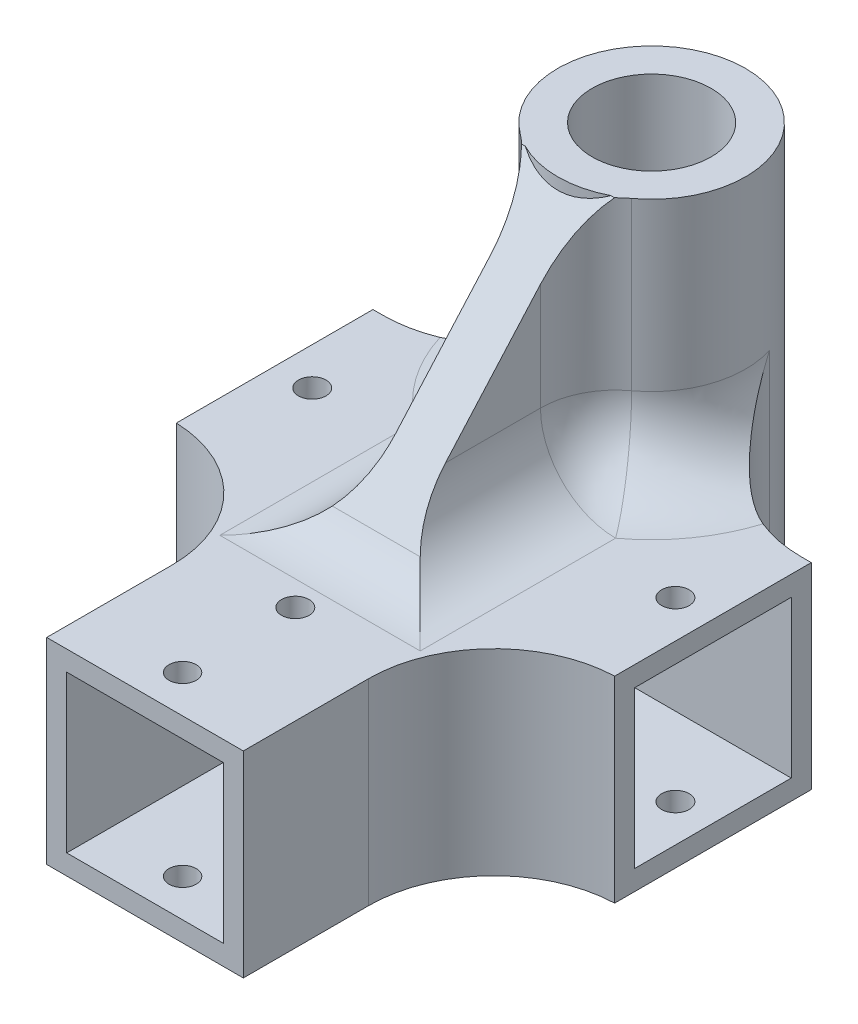
SolidWorks part; units mm, degrees
ref_plane "Front" through (0, 0, 0) normal (0, 0, 1) x (1, 0, 0)
ref_plane "Top" through (0, 0, 0) normal (0, 1, 0) x (1, 0, 0)
ref_plane "Right" through (0, 0, 0) normal (1, 0, 0) x (0, 0, -1)
sketch "Эскиз1" plane through (0, 0, 0) normal (1, 0, 0) x (0, 0, -1)
  line L1 (-12.5, -12.5) -> (12.5, -12.5)
  line L2 (-12.5, -12.5) -> (-12.5, 12.5)
  line L3 (-12.5, 12.5) -> (12.5, 12.5)
  line L4 (12.5, -12.5) -> (12.5, 12.5)
  line L5 (-12.5, -12.5) -> (12.5, 12.5) construction
  line L6 (-12.5, 12.5) -> (12.5, -12.5) construction
  point P0 (0, 0)
  dimension "D1" = 25
  dimension "D2" = 25
extrude "Вытянуть-Тонкостенный1" add sketch "Эскиз1" along normal blind 70 thin thin type one direction wall 3.2
sketch "Эскиз2" plane through (0, 0, 15.7) normal (0, 0, 1) x (1, 0, 0)
  line L0 (35, 15.7) -> (35, -15.7) construction
  line L1 (70, 15.7) -> (0, 15.7) construction
  line L2 (70, -15.7) -> (0, -15.7) construction
  line L4 (22.5, 12.5) -> (47.5, 12.5)
  line L5 (22.5, 12.5) -> (22.5, -12.5)
  line L6 (22.5, -12.5) -> (47.5, -12.5)
  line L7 (47.5, 12.5) -> (47.5, -12.5)
  line L8 (22.5, 12.5) -> (47.5, -12.5) construction
  line L9 (22.5, -12.5) -> (47.5, 12.5) construction
  point P6 (35, 0)
  dimension "D1" = 25
  dimension "D2" = 25
extrude "Вытянуть-Тонкостенный2" add sketch "Эскиз2" along normal blind 40 thin thin type one direction wall 3.2
sketch "Эскиз3" plane through (0, 0, 15.7) normal (0, 0, 1) x (1, 0, 0)
  line L1 (22.5, 12.5) -> (47.5, 12.5)
  line L2 (22.5, 12.5) -> (22.5, -12.5)
  line L3 (22.5, -12.5) -> (47.5, -12.5)
  line L4 (47.5, 12.5) -> (47.5, -12.5)
extrude "Вырез-Вытянуть1" cut sketch "Эскиз3" against normal up to next
fillet "Скругление1" radius 20 2 edges at (50.7, 0, 15.7) (19.3, 0, 15.7)
sketch "Эскиз4" plane through (0, -15.7, 0) normal (0, -1, 0) x (1, 0, 0)
  line L0 (35, 55.7) -> (35, -32.8587) construction
  line L1 (19.3, 55.7) -> (50.7, 55.7) construction
  line L2 (70, -15.7) -> (0, -15.7) construction
  circle A0 centre (35, -25.2) radius 9.5
  circle A1 centre (35, -25.2) radius 15
  dimension "D1" = 19
  dimension "D2" = 9.5
extrude "Бобышка-Вытянуть1" add sketch "Эскиз4" against normal blind 70
sketch "Эскиз5" plane through (0, 0, 0) normal (-1, 0, 0) x (0, 0, 1)
  line L1 (-12.5, 12.5) -> (-10.2, 12.5)
  line L2 (-12.5, 12.5) -> (-12.5, -12.5)
  line L3 (-12.5, -12.5) -> (-10.2, -12.5)
  line L4 (-10.2, 12.5) -> (-10.2, -12.5)
extrude "Вырез-Вытянуть2" cut sketch "Эскиз5" against normal up to next
sketch "Эскиз6" plane through (0, 0, 0) normal (-1, 0, 0) x (0, 0, 1)
  line L0 (-11.8488, 54.3) -> (-11.8488, 15.7)
  line L1 (-11.8488, 54.3) -> (22.349, 15.7)
  line L2 (-15.7, 15.7) -> (15.7, 15.7) construction
  line L3 (-11.8488, 15.7) -> (22.349, 15.7)
  line L5 (-10.2, 54.3) -> (-40.2, 54.3) construction
  line L8 (35.6877, 15.7) -> (15.7, 15.7) construction
extrude "Бобышка-Вытянуть3" add sketch "Эскиз6" against normal blind 8 from offset 31 offset against normal yes
fillet "Скругление2" radius 12 3 edges at (31, 34.376, -10.7432) (39, 34.376, -10.7432) (35, 15.7, 22.349)
fillet "Скругление3" radius 12 6 edges at (39, 15.7, 12.1491) (40.2917, 15.7, -8.8675) (31, 15.7, 12.1491) (29.7083, 15.7, -8.8675) (45.3296, 15.7, -14.3234) (24.6704, 15.7, -14.3234)
sketch "Эскиз7" plane through (0, 15.7, 0) normal (0, 1, 0) x (1, 0, 0)
  line L0 (0, 0) -> (70, 0) construction
  line L1 (0, 15.7) -> (0, -15.7) construction
  line L2 (70, 15.7) -> (70, -15.7) construction
  line L3 (35, -55.7) -> (35, 0) construction
  line L4 (50.7, -55.7) -> (19.3, -55.7) construction
  circle A0 centre (6, 0) radius 2.2
  circle A1 centre (64, 0) radius 2.2
  circle A2 centre (35, -49.7) radius 2.1719
  circle A3 centre (35, -31.7) radius 2.2
  dimension "D1" = 6
  dimension "D2" = 6
  dimension "D3" = 6
  dimension "D4" = 24
extrude "Вырез-Вытянуть3" cut sketch "Эскиз7" against normal through all
fillet "Скругление4" radius 20 2 edges at (46.6082, 6, -15.7) (23.3918, 6, -15.7)
